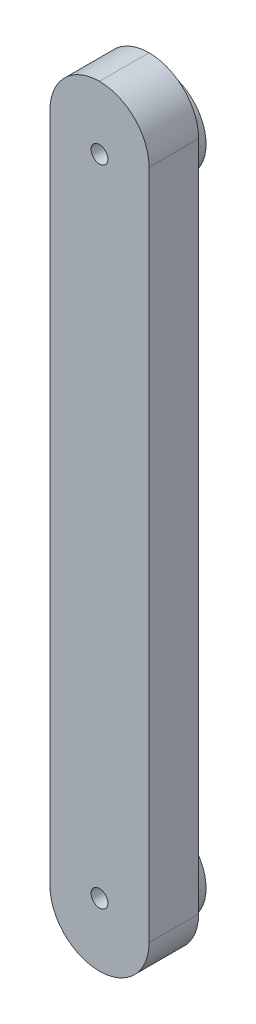
SolidWorks part; units mm, degrees
material "PETG"
ref_plane "Front Plane" through (0, 0, 0) normal (0, 0, 1) x (1, 0, 0)
ref_plane "Top Plane" through (0, 0, 0) normal (0, 1, 0) x (1, 0, 0)
ref_plane "Right Plane" through (0, 0, 0) normal (1, 0, 0) x (0, 0, -1)
sketch "Sketch1" plane through (0, 0, 0) normal (0, 0, 1) x (1, 0, 0)
  line L1 (-10, 77.75) -> (10, 77.75)
  line L2 (-10, 77.75) -> (-10, -77.75)
  line L3 (-10, -77.75) -> (10, -77.75)
  line L4 (10, 77.75) -> (10, -77.75)
  point P8 (-10, 0)
  point P9 (0, 77.75)
  dimension "D1" = 20
  dimension "D2" = 155.5
extrude "Boss-Extrude1" add sketch "Sketch1" along normal blind 10
sketch "Sketch2" plane through (0, 0, 0) normal (0, 0, -1) x (-1, 0, 0)
  line L0 (0, 65) -> (0, -65) construction
  circle A0 centre (0, 65) radius 9
  circle A1 centre (0, -65) radius 9
  dimension "D1" = 130
  dimension "D2" = 18
extrude "Boss-Extrude2" add sketch "Sketch2" along normal blind 2.5
sketch "Sketch3" plane through (0, 0, -2.5) normal (0, 0, -1) x (-1, 0, 0)
  circle A0 centre (0, 65) radius 1.7
  circle A1 centre (0, -65) radius 1.7
  circle A2 centre (0, -65) radius 9 construction
  circle A3 centre (0, 65) radius 9 construction
  dimension "D1" = 3.4
extrude "Cut-Extrude1" cut sketch "Sketch3" against normal through all
fillet "Fillet1" radius 10 4 edges at (10, -77.75, 5) (-10, -77.75, 5) (-10, 77.75, 5) (10, 77.75, 5)
equation "\"tol_dia_id_intfc\" = 0.0200mm ' For hole diameters - Interference fit"
equation "\"tol_dia_id_slip\"  = 0.0300mm ' For hole diameters - Slip fit"
equation "\"tol_dia_id_clear\" = 0.0500mm ' For hole diameters - Clearance fit"
equation "\"tol_dia_od_intfc\" = 0.0200mm ' For shaft diameters - Interference fit"
equation "\"tol_dia_od_slip\"  = 0.0300mm ' For shaft diameters - Slip fit"
equation "\"tol_dia_od_clear\" = 0.0500mm ' For shaft diameters - Clearance fit"
equation "\"tol_general_intfc\"= 0.0030mm ' For general parts (Horiz) - Interference fit"
equation "\"tol_general_slip\" = 0.0050mm ' For general parts (Horiz) - Slip fit"
equation "\"tol_general_clear\"= 0.0100mm ' For general parts (Horiz) - Clearance fit"
equation "\"tol_layer_intfc\"  = 0.0030mm ' For all parts (Vert) - Interference fit"
equation "\"tol_layer_slip\"   = 0.0050mm ' For all parts (Vert) - Slip fit"
equation "\"tol_layer_clear\"  = 0.0100mm ' For all parts (Vert) - Clearance fit"
equation "\"tol_corner_rad\"   = 0.100mm ' For corners that fit into other parts"
